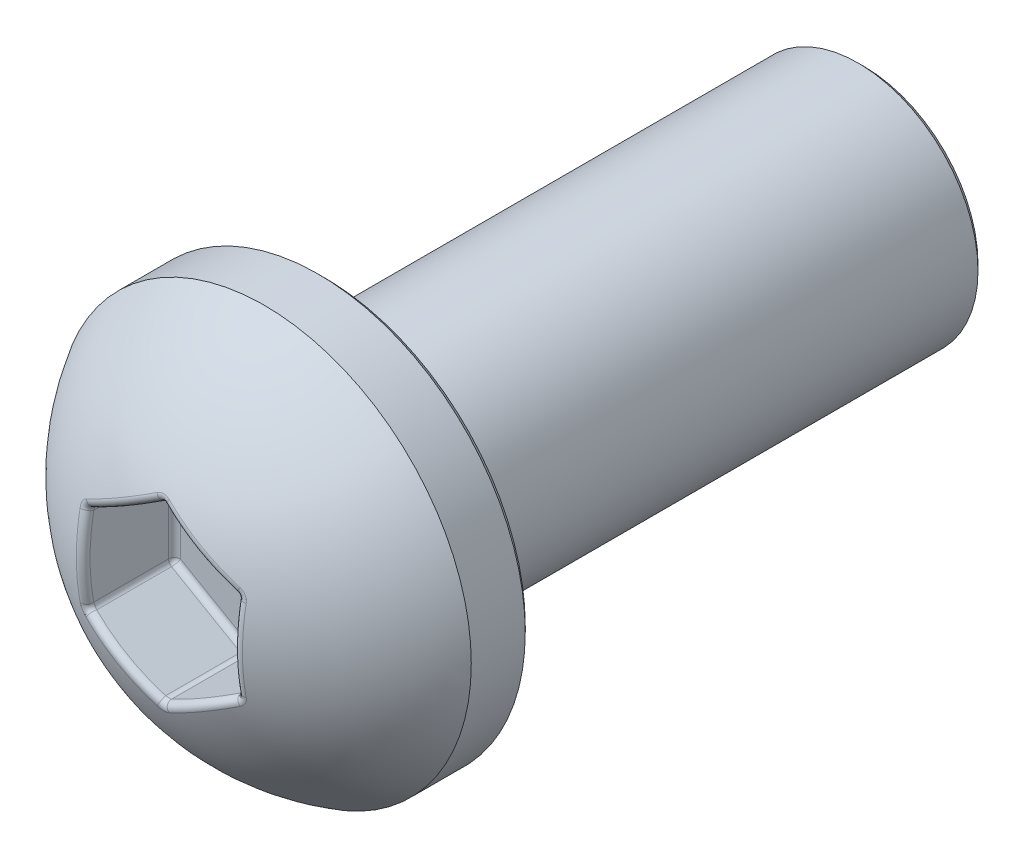
SolidWorks part; units mm, degrees
material "1.4000 (X6Cr13)"
ref_plane "Ebene vorne" through (0, 0, 0) normal (0, 0, 1) x (1, 0, 0)
ref_plane "Ebene oben" through (0, 0, 0) normal (0, 1, 0) x (1, 0, 0)
ref_plane "Ebene rechts" through (0, 0, 0) normal (1, 0, 0) x (0, 0, -1)
sketch "Skizze1" plane through (0, 0, 0) normal (1, 0, 0) x (0, 0, -1)
  line L0 (-21.9199, 0) -> (33.7608, 0) construction
  line L1 (0, 13.9907) -> (0, -9.4798) construction
  line L3 (-2, 6.9) -> (0, 6.9)
  line L4 (0, 6.9) -> (0, 4)
  line L5 (0, 4) -> (18, 4)
  line L6 (18, 4) -> (18, 0)
  line L7 (18, 0) -> (-6, 0)
  arc A0 (-2, 6.9) -> (-6, 0) centre (1.9513, 0) ccw
  point P14 (0, 0)
  point P15 (0, 0)
  dimension "D5" = 2
  dimension "D1" = 8
  dimension "D2" = 6
  dimension "D3" = 13.8
  dimension "D4" = 18
revolve "Rotation1" add sketch "Skizze1" angle 360 about L0
ref_plane "Ebene1" through (0, 0, 6) normal (0, 0, 1) x (1, 0, 0)
sketch "Skizze2" plane through (0, 0, 6) normal (0, 0, 1) x (1, 0, 0)
  line L0 (0, 8.6995) -> (0, -7.3778) construction
  line L1 (2.5, -1.4434) -> (2.5, 1.4434)
  line L2 (2.5, 1.4434) -> (0, 2.8868)
  line L3 (0, 2.8868) -> (-2.5, 1.4434)
  line L4 (-2.5, 1.4434) -> (-2.5, -1.4434)
  line L5 (-2.5, -1.4434) -> (0, -2.8868)
  line L6 (0, -2.8868) -> (2.5, -1.4434)
  circle A0 centre (0, 0) radius 2.5 construction
  dimension "D1" = 5
extrude "Schnitt-Linear austragen1" cut sketch "Skizze2" against normal blind 3.5
chamfer "Fase1" distance 0.2 angle 45 2 edges at (6.9, 0, 0) (4, 0, -18)
fillet "Verrundung1" radius 0.2 19 edges at (-1.25, -2.1651, 2.5) (-2.5, 0, 2.5) (-1.25, 2.1651, 2.5) (1.25, 2.1651, 2.5) (2.5, 0, 2.5) (1.25, -2.1651, 2.5) (-2.5, -1.4434, 3.9787) (0, -2.8868, 3.9787) (2.5, -1.4434, 3.9787) (2.5, 1.4434, 3.9787) (0, 2.8868, 3.9787) (-2.5, 1.4434, 3.9787) (4, 0, 0) (-1.25, -2.1651, 5.5968) (-2.5, 0, 5.5968) (1.25, -2.1651, 5.5968) (-1.25, 2.1651, 5.5968) (2.5, 0, 5.5968) (1.25, 2.1651, 5.5968)
ref_axis "Achse1" through (0, 0, -19.6323) along (0, 0, 1)
